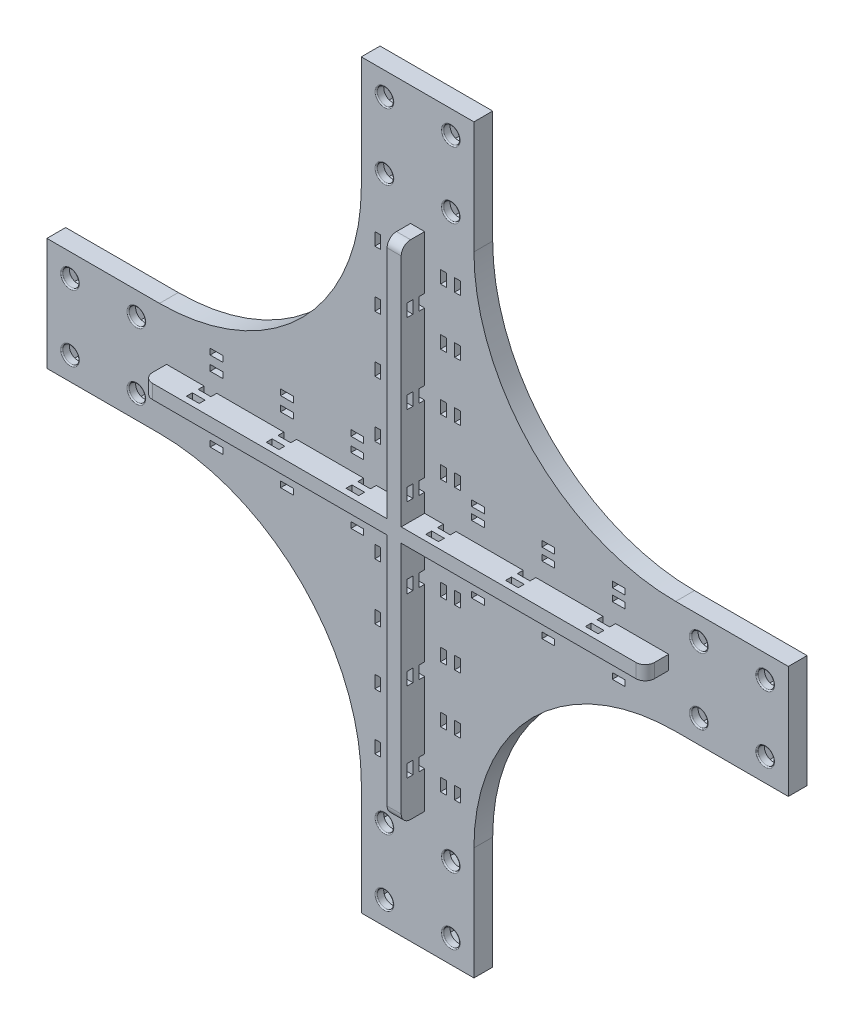
SolidWorks part; units mm, degrees
material "ABS"
ref_plane "Front Plane" through (0, 0, 0) normal (0, 0, 1) x (1, 0, 0)
ref_plane "Top Plane" through (0, 0, 0) normal (0, 1, 0) x (1, 0, 0)
ref_plane "Right Plane" through (0, 0, 0) normal (1, 0, 0) x (0, 0, -1)
sketch "Sketch4" plane through (0, 0, 0) normal (0, 0, 1) x (1, 0, 0)
  line L0 (55.9894, -59.0068) -> (55.9894, 19.0503) construction
  line L1 (-3.6, -59.9497) -> (143.9037, -59.9497) construction
  line L2 (43.9894, 19.0503) -> (67.9894, 19.0503)
  line L3 (-23.0106, -47.9497) -> (-23.0106, -71.9497)
  line L4 (134.9894, -47.9497) -> (134.9894, -71.9497)
  line L5 (43.9894, -138.9497) -> (67.9894, -138.9497)
  line L6 (43.9894, 19.0503) -> (43.9894, -4.9497)
  line L8 (67.9894, -4.9497) -> (67.9894, 19.0503)
  line L9 (-23.0106, -47.9497) -> (0.9894, -47.9497)
  line L11 (0.9894, -71.9497) -> (-23.0106, -71.9497)
  line L12 (43.9894, -138.9497) -> (43.9894, -114.9497)
  line L14 (67.9894, -114.9497) -> (67.9894, -138.9497)
  line L15 (134.9894, -47.9497) -> (110.9894, -47.9497)
  line L17 (110.9894, -71.9497) -> (134.9894, -71.9497)
  arc A0 (0.9894, -47.9497) -> (43.9894, -4.9497) centre (0.9894, -4.9497) ccw
  arc A1 (0.9894, -71.9497) -> (43.9894, -114.9497) centre (0.9894, -114.9497) cw
  arc A2 (67.9894, -114.9497) -> (110.9894, -71.9497) centre (110.9894, -114.9497) cw
  arc A3 (110.9894, -47.9497) -> (67.9894, -4.9497) centre (110.9894, -4.9497) cw
  point P7 (55.9894, 19.0503)
  point P10 (-23.0106, -59.9497)
  point P13 (134.9894, -59.9497)
  point P16 (55.9894, -138.9497)
  dimension "D1" = 24
  dimension "D2" = 24
  dimension "D3" = 110
  dimension "D4" = 110
  dimension "D5" = 55
  dimension "D6" = 55
extrude "Base of drone" add sketch "Sketch4" along normal blind 4
sketch "Sketch5" plane through (0, 0, 4) normal (0, 0, 1) x (1, 0, 0)
  line L0 (55.9894, 19.0503) -> (55.9894, -138.9497) construction
  line L1 (67.9894, 19.0503) -> (43.9894, 19.0503) construction
  line L2 (43.9894, -138.9497) -> (67.9894, -138.9497) construction
  line L3 (-23.0106, -59.9497) -> (134.9894, -59.9497) construction
  line L4 (-23.0106, -47.9497) -> (-23.0106, -71.9497) construction
  line L5 (134.9894, -71.9497) -> (134.9894, -47.9497) construction
  line L6 (43.9894, 19.0503) -> (67.9894, -4.9497) construction
  line L7 (67.9894, 19.0503) -> (43.9894, -4.9497) construction
  line L8 (-23.0106, -47.9497) -> (0.9894, -71.9497) construction
  line L9 (-23.0106, -71.9497) -> (0.9894, -47.9497) construction
  line L10 (0.9894, -47.9497) -> (-23.0106, -47.9497) construction
  line L11 (43.9894, -138.9497) -> (67.9894, -114.9497) construction
  line L12 (67.9894, -138.9497) -> (43.9894, -114.9497) construction
  line L13 (134.9894, -71.9497) -> (110.9894, -47.9497) construction
  line L14 (134.9894, -47.9497) -> (110.9894, -71.9497) construction
  arc A0 (0.9894, -47.9497) -> (43.9894, -4.9497) centre (0.9894, -4.9497) ccw construction
  circle A1 centre (48.9184, 14.1214) radius 1.75
  circle A2 centre (63.0605, 14.1214) radius 1.75
  circle A3 centre (63.0605, -0.0208) radius 1.75
  circle A4 centre (48.9184, -0.0208) radius 1.75
  circle A5 centre (-18.0816, -52.8786) radius 1.75
  circle A6 centre (-3.9395, -52.8786) radius 1.75
  circle A7 centre (-3.9395, -67.0208) radius 1.75
  circle A8 centre (-18.0816, -67.0208) radius 1.75
  circle A9 centre (48.9184, -119.8786) radius 1.75
  circle A10 centre (63.0605, -119.8786) radius 1.75
  circle A11 centre (63.0605, -134.0208) radius 1.75
  circle A12 centre (48.9184, -134.0208) radius 1.75
  circle A13 centre (115.9184, -52.8786) radius 1.75
  circle A14 centre (130.0605, -52.8786) radius 1.75
  circle A15 centre (115.9184, -67.0208) radius 1.75
  circle A16 centre (130.0605, -67.0208) radius 1.75
  dimension "D1" = 3.5
  dimension "D2" = 10
  dimension "D3" = 10
  dimension "D4" = 10
  dimension "D5" = 10
  dimension "D6" = 10
  dimension "D7" = 10
  dimension "D8" = 10
  dimension "D9" = 10
  dimension "D10" = 10
  dimension "D11" = 10
  dimension "D12" = 10
  dimension "D13" = 10
  dimension "D14" = 10
  dimension "D15" = 10
  dimension "D16" = 10
  dimension "D17" = 10
extrude "Screw holes" cut sketch "Sketch5" against normal up to surface (4 mm away) up to face at (55.9894, -59.9497, 0)
sketch "Sketch7" plane through (0, 0, 4) normal (0, 0, 1) x (1, 0, 0)
  line L0 (2.4894, -58.4497) -> (54.4894, -58.4497)
  line L2 (54.4894, -58.4497) -> (54.4894, -6.4497)
  line L3 (43.9894, -4.9497) -> (67.9894, -4.9497) construction
  line L5 (57.4894, -6.4497) -> (57.4894, -58.4497)
  line L6 (57.4894, -58.4497) -> (109.4894, -58.4497)
  line L7 (43.9894, 19.0503) -> (43.9894, -4.9497) construction
  line L9 (109.4894, -61.4497) -> (57.4894, -61.4497)
  line L10 (57.4894, -61.4497) -> (57.4894, -113.4497)
  line L11 (67.9894, -4.9497) -> (67.9894, 19.0503) construction
  line L13 (54.4894, -113.4497) -> (54.4894, -61.4497)
  line L14 (54.4894, -61.4497) -> (2.4894, -61.4497)
  line L16 (2.4894, -58.4497) -> (2.4894, -61.4497)
  line L17 (54.4894, -113.4497) -> (57.4894, -113.4497)
  line L18 (109.4894, -58.4497) -> (109.4894, -61.4497)
  line L19 (54.4894, -6.4497) -> (57.4894, -6.4497)
  line L20 (67.9894, 19.0503) -> (43.9894, 19.0503) construction
  line L21 (0.9894, -47.9497) -> (0.9894, -71.9497) construction
  line L22 (0.9894, -47.9497) -> (-23.0106, -47.9497) construction
  line L23 (-23.0106, -71.9497) -> (0.9894, -71.9497) construction
  line L24 (110.9894, -47.9497) -> (110.9894, -71.9497) construction
  line L25 (134.9894, -47.9497) -> (110.9894, -47.9497) construction
  line L26 (110.9894, -71.9497) -> (134.9894, -71.9497) construction
  line L27 (43.9894, -114.9497) -> (67.9894, -114.9497) construction
  line L28 (43.9894, -114.9497) -> (43.9894, -138.9497) construction
  line L29 (67.9894, -138.9497) -> (67.9894, -114.9497) construction
  line L30 (-23.0106, -47.9497) -> (-23.0106, -71.9497) construction
  line L31 (43.9894, -138.9497) -> (67.9894, -138.9497) construction
  line L32 (134.9894, -71.9497) -> (134.9894, -47.9497) construction
  point P47 (109.4894, -59.9497)
  point P54 (2.4894, -59.9497)
  point P55 (55.9894, -113.4497)
  point P56 (55.9894, -6.4497)
  dimension "D1" = 24
  dimension "D2" = 1.5
  dimension "D3" = 1.5
  dimension "D4" = 1.5
  dimension "D5" = 1.5
  dimension "D6" = 24
  dimension "D7" = 24
  dimension "D8" = 24
  dimension "D9" = 12
  dimension "D10" = 12
  dimension "D11" = 12
  dimension "D12" = 12
fillet "Screw fillet" radius 0.25 16 edges at (-16.3316, -52.8786, 4) (-2.1895, -52.8786, 4) (-2.1895, -67.0208, 4) (-16.3316, -67.0208, 4) (64.8105, -119.8786, 4) (64.8105, -134.0208, 4) (50.6684, -134.0208, 4) (50.6684, -119.8786, 4) (131.8105, -67.0208, 4) (117.6684, -67.0208, 4) (117.6684, -52.8786, 4) (131.8105, -52.8786, 4) (50.6684, -0.0208, 4) (64.8105, -0.0208, 4) (50.6684, 14.1214, 4) (64.8105, 14.1214, 4)
extrude "Drone base spine" add sketch "Sketch7" along normal blind 5 contours L0 L2 L19 L5 L6 L18 L9 L10 L17 L13 L14 L16
fillet "Drone base spine fillet" radius 2 4 edges at (55.9894, -6.4497, 9) (109.4894, -59.9497, 9) (2.4894, -59.9497, 9) (55.9894, -113.4497, 9)
sketch "Sketch8" plane through (57.4894, 0, 0) normal (1, 0, 0) x (0, 0, -1)
  line L0 (-7, -113.4497) -> (-4, -113.4497) construction
  line L1 (-7.75, -102.7497) -> (-6.5, -102.7497)
  line L2 (-7.75, -102.7497) -> (-7.75, -105.4497)
  line L3 (-7.75, -105.4497) -> (-6.5, -105.4497)
  line L4 (-6.5, -102.7497) -> (-6.5, -105.4497)
  line L5 (-9, -61.4497) -> (-9, -111.4497) construction
  line L6 (-4, -61.4497) -> (-4, -113.4497) construction
  line L7 (-4, -102.8497) -> (-5.25, -102.8497)
  line L8 (-4, -102.8497) -> (-4, -105.5497)
  line L9 (-4, -105.5497) -> (-5.25, -105.5497)
  line L10 (-5.25, -102.8497) -> (-5.25, -105.5497)
  dimension "D1" = 8
  dimension "D6" = 2.7
  dimension "D2" = 1.25
  dimension "D3" = 1.25
  dimension "D4" = 2.7
  dimension "D5" = 1.25
extrude "Cable tie holes set 1" cut sketch "Sketch8" against normal up to surface (3 mm away) up to face at (54.4894, -92.3325, 6.6828)
pattern_linear "LPattern1" count 6 spacing 17 along (0, 1, 0) of "Cable tie holes set 1"
sketch "Sketch9" plane through (0, -61.4497, 0) normal (0, -1, 0) x (-1, 0, 0)
  line L0 (-54.4894, -9) -> (-4.4894, -9) construction
  line L1 (-10.4894, -7.75) -> (-13.1894, -7.75)
  line L2 (-10.4894, -7.75) -> (-10.4894, -6.5)
  line L3 (-10.4894, -6.5) -> (-13.1894, -6.5)
  line L4 (-13.1894, -7.75) -> (-13.1894, -6.5)
  line L5 (-2.4894, -7) -> (-2.4894, -4) construction
  line L6 (-54.4894, -4) -> (-2.4894, -4) construction
  line L7 (-13.1894, -4) -> (-10.4894, -4)
  line L8 (-13.1894, -4) -> (-13.1894, -5.25)
  line L9 (-13.1894, -5.25) -> (-10.4894, -5.25)
  line L10 (-10.4894, -4) -> (-10.4894, -5.25)
  dimension "D4" = 8
  dimension "D5" = 2.7
  dimension "D6" = 1.25
  dimension "D2" = 1.25
  dimension "D1" = 1.25
  dimension "D3" = 2.7
extrude "Cable tie holes set 2" cut sketch "Sketch9" against normal up to surface (3 mm away) contours L1 L4 L3 L2 | L8 L7 L10 L9 up to face at (23.6066, -58.4497, 6.6828)
pattern_linear "LPattern2" count 6 spacing 17 along (1, 0, 0) of "Cable tie holes set 2"
sketch "Sketch10" plane through (0, 0, 0) normal (0, 0, -1) x (-1, 0, 0)
  line L0 (-134.9894, -47.9497) -> (-110.9894, -47.9497) construction
  line L1 (-127.116, -52.8786) -> (-128.5883, -50.3286)
  line L2 (-128.5883, -50.3286) -> (-131.5327, -50.3286)
  line L3 (-131.5327, -50.3286) -> (-133.005, -52.8786)
  line L4 (-133.005, -52.8786) -> (-131.5327, -55.4286)
  line L5 (-131.5327, -55.4286) -> (-128.5883, -55.4286)
  line L6 (-128.5883, -55.4286) -> (-127.116, -52.8786)
  line L7 (-112.9739, -52.8786) -> (-114.4461, -50.3286)
  line L8 (-114.4461, -50.3286) -> (-117.3906, -50.3286)
  line L9 (-117.3906, -50.3286) -> (-118.8628, -52.8786)
  line L10 (-118.8628, -52.8786) -> (-117.3906, -55.4286)
  line L11 (-117.3906, -55.4286) -> (-114.4461, -55.4286)
  line L12 (-114.4461, -55.4286) -> (-112.9739, -52.8786)
  line L13 (-127.116, -67.0208) -> (-128.5883, -64.4708)
  line L14 (-128.5883, -64.4708) -> (-131.5327, -64.4708)
  line L15 (-131.5327, -64.4708) -> (-133.005, -67.0208)
  line L16 (-133.005, -67.0208) -> (-131.5327, -69.5708)
  line L17 (-131.5327, -69.5708) -> (-128.5883, -69.5708)
  line L18 (-128.5883, -69.5708) -> (-127.116, -67.0208)
  line L19 (-112.9739, -67.0208) -> (-114.4461, -64.4708)
  line L20 (-114.4461, -64.4708) -> (-117.3906, -64.4708)
  line L21 (-117.3906, -64.4708) -> (-118.8628, -67.0208)
  line L22 (-118.8628, -67.0208) -> (-117.3906, -69.5708)
  line L23 (-117.3906, -69.5708) -> (-114.4461, -69.5708)
  line L24 (-114.4461, -69.5708) -> (-112.9739, -67.0208)
  circle A0 centre (-130.0605, -52.8786) radius 2.55 construction
  circle A1 centre (-115.9184, -52.8786) radius 2.55 construction
  circle A2 centre (-130.0605, -67.0208) radius 2.55 construction
  circle A3 centre (-115.9184, -67.0208) radius 2.55 construction
  dimension "D1" = 5.1
extrude "Hex cut 1" cut sketch "Sketch10" against normal blind 2.4
sketch "Sketch11" plane through (0, 0, 0) normal (0, 0, -1) x (-1, 0, 0)
  line L0 (-67.9894, 19.0503) -> (-43.9894, 19.0503) construction
  line L1 (-60.116, 14.1214) -> (-61.5883, 16.6714)
  line L2 (-61.5883, 16.6714) -> (-64.5327, 16.6714)
  line L3 (-64.5327, 16.6714) -> (-66.005, 14.1214)
  line L4 (-66.005, 14.1214) -> (-64.5327, 11.5714)
  line L5 (-64.5327, 11.5714) -> (-61.5883, 11.5714)
  line L6 (-61.5883, 11.5714) -> (-60.116, 14.1214)
  line L7 (-47.4461, 11.5714) -> (-45.9739, 14.1214)
  line L8 (-45.9739, 14.1214) -> (-47.4461, 16.6714)
  line L9 (-47.4461, 16.6714) -> (-50.3906, 16.6714)
  line L10 (-50.3906, 16.6714) -> (-51.8628, 14.1214)
  line L11 (-51.8628, 14.1214) -> (-50.3906, 11.5714)
  line L12 (-50.3906, 11.5714) -> (-47.4461, 11.5714)
  line L13 (-60.116, -0.0208) -> (-61.5883, 2.5292)
  line L14 (-61.5883, 2.5292) -> (-64.5327, 2.5292)
  line L15 (-64.5327, 2.5292) -> (-66.005, -0.0208)
  line L16 (-66.005, -0.0208) -> (-64.5327, -2.5708)
  line L17 (-64.5327, -2.5708) -> (-61.5883, -2.5708)
  line L18 (-61.5883, -2.5708) -> (-60.116, -0.0208)
  line L19 (-45.9739, -0.0208) -> (-47.4461, 2.5292)
  line L20 (-47.4461, 2.5292) -> (-50.3906, 2.5292)
  line L21 (-50.3906, 2.5292) -> (-51.8628, -0.0208)
  line L22 (-51.8628, -0.0208) -> (-50.3906, -2.5708)
  line L23 (-50.3906, -2.5708) -> (-47.4461, -2.5708)
  line L24 (-47.4461, -2.5708) -> (-45.9739, -0.0208)
  circle A0 centre (-63.0605, 14.1214) radius 2.55 construction
  circle A1 centre (-48.9184, 14.1214) radius 2.55 construction
  circle A2 centre (-63.0605, -0.0208) radius 2.55 construction
  circle A3 centre (-48.9184, -0.0208) radius 2.55 construction
  dimension "D1" = 5.1
extrude "Hex cut 2" cut sketch "Sketch11" against normal blind 2.4
sketch "Sketch12" plane through (0, 0, 0) normal (0, 0, -1) x (-1, 0, 0)
  line L0 (-0.9894, -47.9497) -> (23.0106, -47.9497) construction
  line L1 (6.884, -52.8786) -> (5.4117, -50.3286)
  line L2 (5.4117, -50.3286) -> (2.4673, -50.3286)
  line L3 (2.4673, -50.3286) -> (0.995, -52.8786)
  line L4 (0.995, -52.8786) -> (2.4673, -55.4286)
  line L5 (2.4673, -55.4286) -> (5.4117, -55.4286)
  line L6 (5.4117, -55.4286) -> (6.884, -52.8786)
  line L7 (21.0261, -52.8786) -> (19.5539, -50.3286)
  line L8 (19.5539, -50.3286) -> (16.6094, -50.3286)
  line L9 (16.6094, -50.3286) -> (15.1372, -52.8786)
  line L10 (15.1372, -52.8786) -> (16.6094, -55.4286)
  line L11 (16.6094, -55.4286) -> (19.5539, -55.4286)
  line L12 (19.5539, -55.4286) -> (21.0261, -52.8786)
  line L13 (6.884, -67.0208) -> (5.4117, -64.4708)
  line L14 (5.4117, -64.4708) -> (2.4673, -64.4708)
  line L15 (2.4673, -64.4708) -> (0.995, -67.0208)
  line L16 (0.995, -67.0208) -> (2.4673, -69.5708)
  line L17 (2.4673, -69.5708) -> (5.4117, -69.5708)
  line L18 (5.4117, -69.5708) -> (6.884, -67.0208)
  line L19 (21.0261, -67.0208) -> (19.5539, -64.4708)
  line L20 (19.5539, -64.4708) -> (16.6094, -64.4708)
  line L21 (16.6094, -64.4708) -> (15.1372, -67.0208)
  line L22 (15.1372, -67.0208) -> (16.6094, -69.5708)
  line L23 (16.6094, -69.5708) -> (19.5539, -69.5708)
  line L24 (19.5539, -69.5708) -> (21.0261, -67.0208)
  circle A0 centre (3.9395, -52.8786) radius 2.55 construction
  circle A1 centre (18.0816, -52.8786) radius 2.55 construction
  circle A2 centre (3.9395, -67.0208) radius 2.55 construction
  circle A3 centre (18.0816, -67.0208) radius 2.55 construction
  dimension "D1" = 5.1
extrude "Hex cut 3" cut sketch "Sketch12" against normal blind 2.4
sketch "Sketch13" plane through (0, 0, 0) normal (0, 0, -1) x (-1, 0, 0)
  line L0 (-67.9894, -138.9497) -> (-67.9894, -114.9497) construction
  line L1 (-60.5105, -121.3509) -> (-60.5105, -118.4064)
  line L2 (-60.5105, -118.4064) -> (-63.0605, -116.9342)
  line L3 (-63.0605, -116.9342) -> (-65.6105, -118.4064)
  line L4 (-65.6105, -118.4064) -> (-65.6105, -121.3509)
  line L5 (-65.6105, -121.3509) -> (-63.0605, -122.8231)
  line L6 (-63.0605, -122.8231) -> (-60.5105, -121.3509)
  line L7 (-48.9184, -116.9342) -> (-51.4684, -118.4064)
  line L8 (-51.4684, -118.4064) -> (-51.4684, -121.3509)
  line L9 (-51.4684, -121.3509) -> (-48.9184, -122.8231)
  line L10 (-48.9184, -122.8231) -> (-46.3684, -121.3509)
  line L11 (-46.3684, -121.3509) -> (-46.3684, -118.4064)
  line L12 (-46.3684, -118.4064) -> (-48.9184, -116.9342)
  line L13 (-48.9184, -131.0763) -> (-51.4684, -132.5485)
  line L14 (-51.4684, -132.5485) -> (-51.4684, -135.493)
  line L15 (-51.4684, -135.493) -> (-48.9184, -136.9653)
  line L16 (-48.9184, -136.9653) -> (-46.3684, -135.493)
  line L17 (-46.3684, -135.493) -> (-46.3684, -132.5485)
  line L18 (-46.3684, -132.5485) -> (-48.9184, -131.0763)
  line L19 (-63.0605, -131.0763) -> (-65.6105, -132.5485)
  line L20 (-65.6105, -132.5485) -> (-65.6105, -135.493)
  line L21 (-65.6105, -135.493) -> (-63.0605, -136.9653)
  line L22 (-63.0605, -136.9653) -> (-60.5105, -135.493)
  line L23 (-60.5105, -135.493) -> (-60.5105, -132.5485)
  line L24 (-60.5105, -132.5485) -> (-63.0605, -131.0763)
  circle A0 centre (-63.0605, -119.8786) radius 2.55 construction
  circle A1 centre (-48.9184, -119.8786) radius 2.55 construction
  circle A2 centre (-48.9184, -134.0208) radius 2.55 construction
  circle A3 centre (-63.0605, -134.0208) radius 2.55 construction
  dimension "D1" = 5.1
extrude "Hex cut 4" cut sketch "Sketch13" against normal blind 2.4
sketch "Sketch14" plane through (0, 0, 4) normal (0, 0, 1) x (1, 0, 0)
  line L0 (50.4894, -6.4497) -> (50.4894, -58.4497) construction
  line L1 (2.4894, -58.4497) -> (10.4894, -58.4497) construction
  line L2 (47.4894, -58.4497) -> (47.4894, -6.4497) construction
  line L3 (61.4894, -58.4497) -> (61.4894, -6.4497) construction
  line L4 (57.4894, -58.4497) -> (61.4894, -58.4497) construction
  line L5 (64.4894, -58.4497) -> (64.4894, -6.4497) construction
  line L6 (54.4894, -58.4497) -> (54.4894, -8.4497) construction
  line L7 (4.4894, -58.4497) -> (54.4894, -58.4497) construction
  line L8 (57.4894, -8.4497) -> (57.4894, -58.4497) construction
  line L9 (46.8644, -47.7497) -> (48.1144, -47.7497)
  line L10 (46.8644, -47.7497) -> (46.8644, -50.4497)
  line L11 (46.8644, -50.4497) -> (48.1144, -50.4497)
  line L12 (48.1144, -47.7497) -> (48.1144, -50.4497)
  line L13 (49.8644, -47.7497) -> (51.1144, -47.7497)
  line L14 (49.8644, -47.7497) -> (49.8644, -50.4497)
  line L15 (49.8644, -50.4497) -> (51.1144, -50.4497)
  line L16 (51.1144, -47.7497) -> (51.1144, -50.4497)
  line L17 (57.4894, -58.4497) -> (107.4894, -58.4497) construction
  line L18 (60.8644, -47.7497) -> (62.1144, -47.7497)
  line L19 (60.8644, -47.7497) -> (60.8644, -50.4497)
  line L20 (60.8644, -50.4497) -> (62.1144, -50.4497)
  line L21 (62.1144, -47.7497) -> (62.1144, -50.4497)
  line L22 (63.8644, -47.7497) -> (65.1144, -47.7497)
  line L23 (63.8644, -47.7497) -> (63.8644, -50.4497)
  line L24 (63.8644, -50.4497) -> (65.1144, -50.4497)
  line L25 (65.1144, -47.7497) -> (65.1144, -50.4497)
  dimension "D1" = 4
  dimension "D2" = 4
  dimension "D3" = 3
  dimension "D4" = 3
  dimension "D5" = 8
  dimension "D6" = 8
  dimension "D7" = 2.7
  dimension "D8" = 1.25
  dimension "D9" = 0.625
  dimension "D10" = 0.625
  dimension "D11" = 8
  dimension "D12" = 8
  dimension "D13" = 2.7
  dimension "D14" = 2.7
  dimension "D15" = 0.625
  dimension "D16" = 0.625
  dimension "D17" = 1.25
  dimension "D18" = 1.25
extrude "Cut-Extrude8" cut sketch "Sketch14" against normal up to surface (4 mm away) up to face at (63.0605, -134.0208, 0)
pattern_linear "LPattern3" count 4 spacing 12 along (0, 1, 0) of "Cut-Extrude8"
sketch "Sketch15" plane through (0, 0, 4) normal (0, 0, 1) x (1, 0, 0)
  line L0 (47.4894, -61.4497) -> (47.4894, -113.1144) construction
  line L1 (54.4894, -61.4497) -> (4.4894, -61.4497) construction
  line L2 (50.4894, -61.4497) -> (50.4894, -113.1144) construction
  line L3 (54.4894, -61.4497) -> (47.1894, -61.4497) construction
  line L4 (61.4894, -61.4497) -> (61.4894, -113.1144) construction
  line L5 (109.4894, -61.4497) -> (98.1894, -61.4497) construction
  line L6 (64.4894, -61.4497) -> (64.4894, -113.1144) construction
  line L7 (107.4894, -61.4497) -> (57.4894, -61.4497) construction
  line L8 (54.4894, -113.4497) -> (54.4894, -105.5497) construction
  line L9 (46.8644, -69.4497) -> (48.1144, -69.4497)
  line L10 (46.8644, -69.4497) -> (46.8644, -72.1497)
  line L11 (46.8644, -72.1497) -> (48.1144, -72.1497)
  line L12 (48.1144, -69.4497) -> (48.1144, -72.1497)
  line L13 (49.8644, -69.4497) -> (51.1144, -69.4497)
  line L14 (49.8644, -69.4497) -> (49.8644, -72.1497)
  line L15 (49.8644, -72.1497) -> (51.1144, -72.1497)
  line L16 (51.1144, -69.4497) -> (51.1144, -72.1497)
  line L17 (60.8644, -69.4497) -> (62.1144, -69.4497)
  line L18 (60.8644, -69.4497) -> (60.8644, -72.1497)
  line L19 (60.8644, -72.1497) -> (62.1144, -72.1497)
  line L20 (62.1144, -69.4497) -> (62.1144, -72.1497)
  line L21 (63.8644, -69.4497) -> (65.1144, -69.4497)
  line L22 (63.8644, -69.4497) -> (63.8644, -72.1497)
  line L23 (63.8644, -72.1497) -> (65.1144, -72.1497)
  line L24 (65.1144, -69.4497) -> (65.1144, -72.1497)
  line L25 (57.4894, -61.4497) -> (57.4894, -111.4497) construction
  point P32 (64.4894, -69.4497)
  dimension "D9" = 0.625
  dimension "D10" = 0.625
  dimension "D1" = 8
  dimension "D2" = 8
  dimension "D3" = 8
  dimension "D4" = 8
  dimension "D5" = 2.7
  dimension "D6" = 1.25
  dimension "D7" = 0.625
  dimension "D8" = 0.625
  dimension "D11" = 4
  dimension "D12" = 3
  dimension "D13" = 4
  dimension "D14" = 3
extrude "Cut-Extrude9" cut sketch "Sketch15" against normal up to surface (4 mm away) up to face at (50.4894, -37.0997, 0)
pattern_linear "LPattern4" count 4 spacing 12 along (0, -1, 0) of "Cut-Extrude9"
sketch "Sketch16" plane through (0, 0, 4) normal (0, 0, 1) x (1, 0, 0)
  line L0 (54.4894, -54.4497) -> (2.5961, -54.4497) construction
  line L1 (54.4894, -58.4497) -> (54.4894, -54.5497) construction
  line L2 (54.4894, -51.4497) -> (2.5961, -51.4497) construction
  line L3 (54.4894, -58.4497) -> (54.4894, -8.4497) construction
  line L4 (54.4894, -65.4497) -> (2.5961, -65.4497) construction
  line L5 (54.4894, -113.4497) -> (54.4894, -105.5497) construction
  line L6 (54.4894, -68.4497) -> (2.5961, -68.4497) construction
  line L7 (54.4894, -111.4497) -> (54.4894, -61.4497) construction
  line L8 (2.4894, -58.4497) -> (10.4894, -58.4497) construction
  line L9 (54.4894, -61.4497) -> (4.4894, -61.4497) construction
  line L11 (41.7894, -50.8247) -> (44.4894, -50.8247)
  line L12 (41.7894, -50.8247) -> (41.7894, -52.0747)
  line L13 (41.7894, -52.0747) -> (44.4894, -52.0747)
  line L14 (44.4894, -50.8247) -> (44.4894, -52.0747)
  line L15 (41.7894, -53.8247) -> (44.4894, -53.8247)
  line L16 (41.7894, -53.8247) -> (41.7894, -55.0747)
  line L17 (41.7894, -55.0747) -> (44.4894, -55.0747)
  line L18 (44.4894, -53.8247) -> (44.4894, -55.0747)
  line L19 (41.7894, -64.8247) -> (44.4894, -64.8247)
  line L20 (41.7894, -64.8247) -> (41.7894, -66.0747)
  line L21 (41.7894, -66.0747) -> (44.4894, -66.0747)
  line L22 (44.4894, -64.8247) -> (44.4894, -66.0747)
  line L23 (41.7894, -67.8247) -> (44.4894, -67.8247)
  line L24 (41.7894, -67.8247) -> (41.7894, -69.0747)
  line L25 (41.7894, -69.0747) -> (44.4894, -69.0747)
  line L26 (44.4894, -67.8247) -> (44.4894, -69.0747)
  dimension "D5" = 10
  dimension "D6" = 10
  dimension "D7" = 10
  dimension "D8" = 10
  dimension "D1" = 3
  dimension "D2" = 3
  dimension "D3" = 4
  dimension "D4" = 4
  dimension "D9" = 2.7
  dimension "D10" = 2.7
  dimension "D11" = 2.7
  dimension "D12" = 2.7
  dimension "D13" = 1.25
  dimension "D14" = 1.25
  dimension "D15" = 1.25
  dimension "D16" = 1.25
  dimension "D17" = 0.625
  dimension "D18" = 0.625
  dimension "D19" = 0.625
  dimension "D20" = 0.625
extrude "Cut-Extrude10" cut sketch "Sketch16" against normal up to surface (4 mm away) up to face at (50.4894, -82.7997, 0)
pattern_linear "LPattern5" count 3 spacing 15 along (-1, 0, 0) of "Cut-Extrude10"
sketch "Sketch17" plane through (0, 0, 4) normal (0, 0, 1) x (1, 0, 0)
  line L0 (57.4894, -51.5598) -> (108.9591, -51.5598) construction
  line L1 (57.4894, -6.4497) -> (57.4894, -17.8497) construction
  line L2 (57.4894, -54.1212) -> (109.0591, -54.1212) construction
  line L3 (57.4894, -65.4497) -> (108.9591, -65.4497) construction
  line L4 (57.4894, -61.4497) -> (57.4894, -68.8497) construction
  line L5 (57.4894, -68.4497) -> (108.9591, -68.4497) construction
  line L6 (57.4894, -61.4497) -> (57.4894, -111.4497) construction
  line L7 (109.4894, -61.4497) -> (98.1894, -61.4497) construction
  line L8 (67.4894, -50.9348) -> (70.1894, -50.9348)
  line L9 (67.4894, -50.9348) -> (67.4894, -52.1848)
  line L10 (67.4894, -52.1848) -> (70.1894, -52.1848)
  line L11 (70.1894, -50.9348) -> (70.1894, -52.1848)
  line L12 (67.4894, -53.4962) -> (70.1894, -53.4962)
  line L13 (67.4894, -53.4962) -> (67.4894, -54.7462)
  line L14 (67.4894, -54.7462) -> (70.1894, -54.7462)
  line L15 (70.1894, -53.4962) -> (70.1894, -54.7462)
  line L16 (67.4894, -64.8247) -> (70.1894, -64.8247)
  line L17 (67.4894, -64.8247) -> (67.4894, -66.0747)
  line L18 (67.4894, -66.0747) -> (70.1894, -66.0747)
  line L19 (70.1894, -64.8247) -> (70.1894, -66.0747)
  line L20 (67.4894, -67.8247) -> (70.1894, -67.8247)
  line L21 (67.4894, -67.8247) -> (67.4894, -69.0747)
  line L22 (67.4894, -69.0747) -> (70.1894, -69.0747)
  line L23 (70.1894, -67.8247) -> (70.1894, -69.0747)
  point P30 (67.4894, -51.5598)
  dimension "D2" = 10
  dimension "D3" = 10
  dimension "D4" = 10
  dimension "D7" = 2.7
  dimension "D15" = 0.625
  dimension "D16" = 0.625
  dimension "D5" = 2.7
  dimension "D13" = 1.25
  dimension "D18" = 0.625
  dimension "D1" = 10
  dimension "D6" = 2.7
  dimension "D8" = 2.7
  dimension "D9" = 1.25
  dimension "D10" = 1.25
  dimension "D14" = 0.625
  dimension "D17" = 4
  dimension "D12" = 3
  dimension "D11" = 1.25
extrude "Cut-Extrude11" cut sketch "Sketch17" against normal up to surface (4 mm away) up to face at (28.1394, -54.4497, 0)
pattern_linear "LPattern6" count 3 spacing 15 along (1, 0, 0) of "Cut-Extrude11"
equation "\"D3@Sketch5\"=\"D2@Sketch5\""
equation "\"D4@Sketch5\"=\"D2@Sketch5\""
equation "\"D5@Sketch5\"=\"D2@Sketch5\""
equation "\"D7@Sketch5\"=\"D2@Sketch5\""
equation "\"D6@Sketch5\"=\"D2@Sketch5\""
equation "\"D8@Sketch5\"=\"D2@Sketch5\""
equation "\"D9@Sketch5\"=\"D2@Sketch5\""
equation "\"D13@Sketch5\"=\"D2@Sketch5\""
equation "\"D11@Sketch5\"=\"D2@Sketch5\""
equation "\"D12@Sketch5\"=\"D2@Sketch5\""
equation "\"D10@Sketch5\"=\"D2@Sketch5\""
equation "\"D17@Sketch5\"=\"D2@Sketch5\""
equation "\"D14@Sketch5\"=\"D2@Sketch5\""
equation "\"D15@Sketch5\"=\"D2@Sketch5\""
equation "\"D16@Sketch5\"=\"D2@Sketch5\""
equation "\"D4@Sketch4\"=\"D3@Sketch4\""
equation "\"D5@Sketch4\"=\"D3@Sketch4\"/2"
equation "\"D6@Sketch4\"=\"D3@Sketch4\"/2"
equation "\"D3@Sketch7\"=\"D2@Sketch7\""
equation "\"D4@Sketch7\"=\"D2@Sketch7\""
equation "\"D5@Sketch7\"=\"D2@Sketch7\""
equation "\"D6@Sketch7\"=\"D1@Sketch7\""
equation "\"D7@Sketch7\"=\"D1@Sketch7\""
equation "\"D8@Sketch7\"=\"D1@Sketch7\""
equation "\"D9@Sketch7\"=\"D6@Sketch7\"/2"
equation "\"D10@Sketch7\"=\"D8@Sketch7\"/2"
equation "\"D11@Sketch7\"=\"D7@Sketch7\"/2"
equation "\"D12@Sketch7\"=\"D1@Sketch7\"/2"
equation "\"D9@Sketch14\"=\"D8@Sketch14\"/2"
equation "\"D10@Sketch14\"=\"D9@Sketch14\""
equation "\"D11@Sketch14\"=\"D6@Sketch14\""
equation "\"D12@Sketch14\"=\"D6@Sketch14\""
equation "\"D13@Sketch14\"=\"D7@Sketch14\""
equation "\"D14@Sketch14\"=\"D7@Sketch14\""
equation "\"D15@Sketch14\"=\"D9@Sketch14\""
equation "\"D16@Sketch14\"=\"D9@Sketch14\""
equation "\"D17@Sketch14\"=\"D8@Sketch14\""
equation "\"D18@Sketch14\"=\"D8@Sketch14\""
equation "\"D7@Sketch15\"=\"D6@Sketch15\"/2"
equation "\"D8@Sketch15\"=\"D7@Sketch15\""
equation "\"D9@Sketch15\"=\"D7@Sketch15\""
equation "\"D10@Sketch15\"=\"D7@Sketch15\""
equation "\"D13@Sketch15\"=\"D11@Sketch15\""
equation "\"D14@Sketch15\"=\"D12@Sketch15\""
equation "\"D2@Sketch16\"=\"D1@Sketch16\""
equation "\"D4@Sketch16\"=\"D3@Sketch16\""
equation "\"D6@Sketch16\"=\"D5@Sketch16\""
equation "\"D7@Sketch16\"=\"D6@Sketch16\""
equation "\"D8@Sketch16\"=\"D6@Sketch16\""
equation "\"D10@Sketch16\"=\"D9@Sketch16\""
equation "\"D11@Sketch16\"=\"D9@Sketch16\""
equation "\"D12@Sketch16\"=\"D9@Sketch16\""
equation "\"D14@Sketch16\"=\"D13@Sketch16\""
equation "\"D15@Sketch16\"=\"D13@Sketch16\""
equation "\"D16@Sketch16\"=\"D13@Sketch16\""
equation "\"D17@Sketch16\"=\"D13@Sketch16\"/2"
equation "\"D18@Sketch16\"=\"D17@Sketch16\""
equation "\"D19@Sketch16\"=\"D18@Sketch16\""
equation "\"D20@Sketch16\"=\"D15@Sketch16\"/2"
equation "\"D2@Sketch17\"=\"D1@Sketch17\""
equation "\"D3@Sketch17\"=\"D2@Sketch17\""
equation "\"D4@Sketch17\"=\"D2@Sketch17\""
equation "\"D5@Sketch17\"=2.7"
equation "\"D6@Sketch17\"=\"D5@Sketch17\""
equation "\"D7@Sketch17\"=\"D6@Sketch17\""
equation "\"D8@Sketch17\"=\"D6@Sketch17\""
equation "\"D10@Sketch17\"=\"D9@Sketch17\""
equation "\"D14@Sketch17\"=\"D9@Sketch17\"/2"
equation "\"D15@Sketch17\"=\"D10@Sketch17\"/2"
equation "\"D11@Sketch17\"=\"D9@Sketch17\""
equation "\"D13@Sketch17\"=\"D11@Sketch17\""
equation "\"D16@Sketch17\"=\"D13@Sketch17\"/2"
equation "\"D18@Sketch17\"=\"D16@Sketch17\""
equation "\"D5@Sketch8\"=\"D2@Sketch8\""
equation "\"D6@Sketch8\"=\"D4@Sketch8\""
equation "\"D5@Sketch9\"=\"D3@Sketch9\""
equation "\"D6@Sketch9\"=\"D2@Sketch9\""
